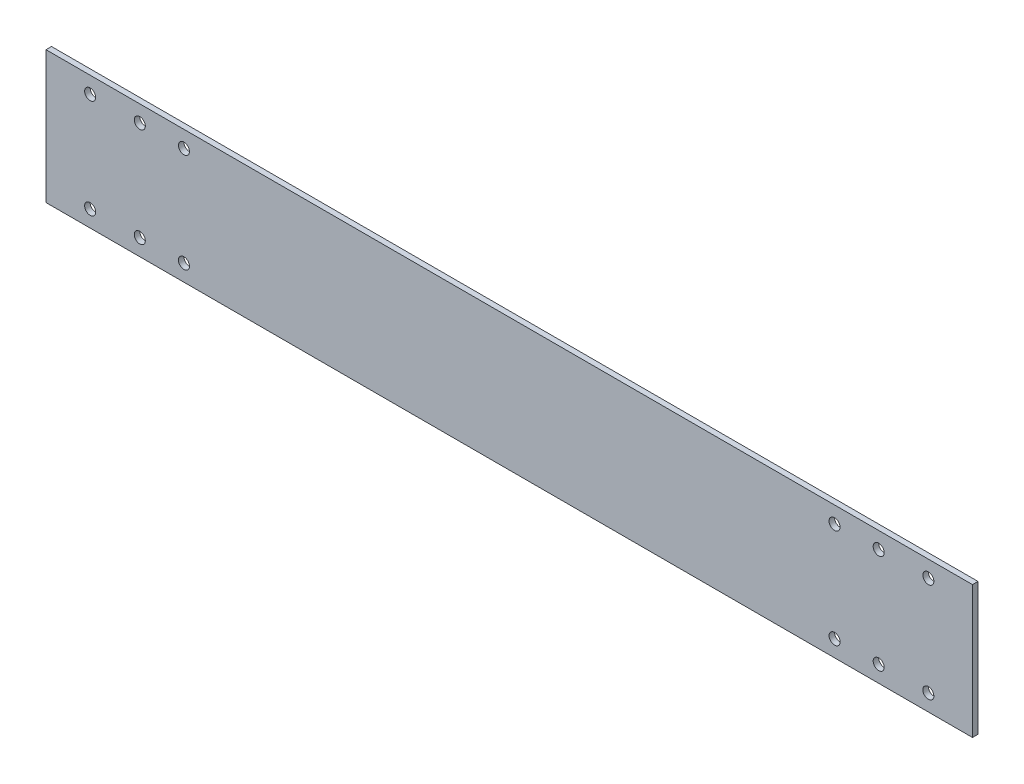
SolidWorks part; units mm, degrees
material "6061-T6 (SS)"
ref_plane "Front Plane" through (0, 0, 0) normal (0, 0, 1) x (1, 0, 0)
ref_plane "Top Plane" through (0, 0, 0) normal (0, 1, 0) x (1, 0, 0)
ref_plane "Right Plane" through (0, 0, 0) normal (1, 0, 0) x (0, 0, -1)
sketch "Sketch1" plane through (0, -330.2, 0) normal (0, 0, 1) x (1, 0, 0)
  line L1 (-247.2046, 6612.1072) -> (285.9414, 6612.1072)
  line L2 (-247.2046, 6612.1072) -> (-247.2046, 6535.9072)
  line L3 (-247.2046, 6535.9072) -> (285.9414, 6535.9072)
  line L4 (285.9414, 6612.1072) -> (285.9414, 6535.9072)
  dimension "D1" = 76.2
  dimension "D2" = 533.146
extrude "Boss-Extrude1" add sketch "Sketch1" along normal blind 3.175
sketch "Sketch2" plane through (0, 0, 0) normal (0, 0, -1) x (-1, 0, 0)
  line L0 (-285.9414, 6281.9072) -> (247.2046, 6281.9072) construction
  line L1 (215.4546, 6281.9072) -> (171.0046, 6281.9072)
  line L2 (215.4546, 6281.9072) -> (215.4546, 6205.7072)
  line L3 (215.4546, 6205.7072) -> (171.0046, 6205.7072)
  line L4 (171.0046, 6281.9072) -> (171.0046, 6205.7072)
  line L5 (247.2046, 6205.7072) -> (-285.9414, 6205.7072) construction
  line L6 (247.2046, 6281.9072) -> (247.2046, 6205.7072) construction
  line L7 (-19.3684, 6281.9072) -> (-19.3684, 6205.7072) construction
  line L8 (-209.7414, 6281.9072) -> (-209.7414, 6205.7072)
  line L9 (-254.1914, 6205.7072) -> (-209.7414, 6205.7072)
  line L10 (-254.1914, 6281.9072) -> (-254.1914, 6205.7072)
  line L11 (-254.1914, 6281.9072) -> (-209.7414, 6281.9072)
  dimension "D1" = 44.45
  dimension "D2" = 31.75
split line "Split Line1" [suppressed]
hole_wizard "1/4 (0.25) Diameter Hole1" positions "Sketch6" profile "Sketch7" hole size "1/4" standard "ANSI Inch" end condition through all
sketch "Sketch6" plane through (0, 0, 0) normal (0, 0, -1) x (-1, 0, 0)
  line L0 (-19.3684, 6281.9072) -> (-19.3684, 6205.7072) construction
  line L1 (-285.9414, 6281.9072) -> (247.2046, 6281.9072) construction
  line L2 (247.2046, 6205.7072) -> (-285.9414, 6205.7072) construction
  line L3 (-285.9414, 6205.7072) -> (-285.9414, 6281.9072) construction
  point P0 (-231.9664, 6215.2322)
  point P3 (-206.5664, 6215.2322)
  point P6 (-206.5664, 6272.3822)
  point P9 (-231.9664, 6272.3822)
  point P27 (-260.5414, 6215.2322)
  point P29 (-260.5414, 6272.3822)
  point P37 (221.8046, 6272.3822)
  point P38 (221.8046, 6215.2322)
  point P39 (193.2296, 6272.3822)
  point P40 (167.8296, 6272.3822)
  point P41 (167.8296, 6215.2322)
  point P42 (193.2296, 6215.2322)
  point P44 (0, 0)
  point P45 (0, 0)
  dimension "D1" = 25.4
sketch "Sketch7" plane through (231.9664, 6215.2322, 0) normal (1, 0, 0) x (0, 1, 0)
  line L0 (0, 0) -> (0, 3.175)
  line L1 (0, 3.175) -> (3.175, 3.175)
  line L2 (3.175, 3.175) -> (3.175, 0)
  line L5 (3.175, 0) -> (0, 0)
  line L11 (0, -6.35) -> (0, 107.95) construction
  dimension "Thru Hole Dia." = 6.35
  dimension "Thru Hole Depth" = 3.175
